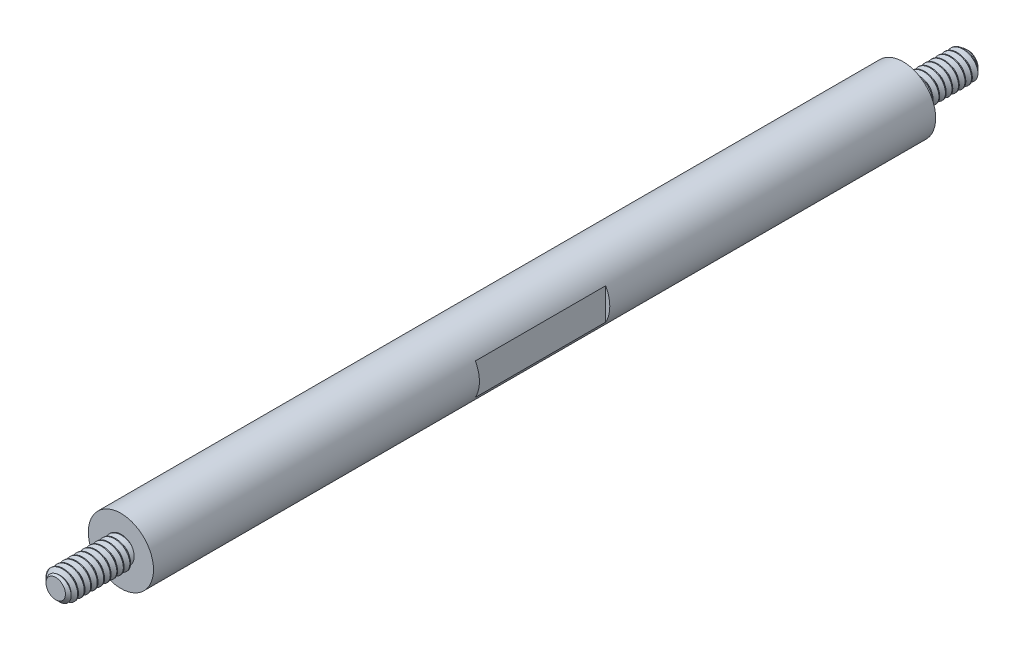
SolidWorks part; units mm, degrees
ref_plane "Front Plane" through (0, 0, 0) normal (0, 0, 1) x (1, 0, 0)
ref_plane "Top Plane" through (0, 0, 0) normal (0, 1, 0) x (1, 0, 0)
ref_plane "Right Plane" through (0, 0, 0) normal (1, 0, 0) x (0, 0, -1)
sketch "Sketch1" plane through (0, 0, 0) normal (0, 0, 1) x (1, 0, 0)
  line L1 (0, 3.6662) -> (-3.175, 1.8331) construction
  line L2 (-3.175, 1.8331) -> (-3.175, -1.8331) construction
  line L3 (-3.175, -1.8331) -> (0, -3.6662) construction
  line L4 (0, -3.6662) -> (3.175, -1.8331) construction
  line L5 (3.175, -1.8331) -> (3.175, 1.8331) construction
  line L6 (3.175, 1.8331) -> (0, 3.6662) construction
  circle A0 centre (0, 0) radius 3.175
  circle A1 centre (0, 0) radius 3.175 construction
  dimension "OD" = 6.35
extrude "Extrude1" add sketch "Sketch1" against normal blind 76.2
sketch "Sketch2" plane through (0, 0, 0) normal (0, 0, 1) x (1, 0, 0)
  circle A2 centre (0, 0) radius 1.4224
  dimension "D1" = 2.8448
extrude "Extrude2" add sketch "Sketch2" along normal blind 6.35 separate body
chamfer "Chamfer1" distance 0.4763 angle 45 1 edges at (1.4224, 0, 6.35)
sketch "Sketch3" plane through (0, 0, 0) normal (0, 0, -1) x (-1, 0, 0)
  circle A1 centre (0, 0) radius 1.4224
  circle A2 centre (0, 0) radius 1.4224
  point P0 (0, 1.4224)
  dimension "D1" = 0
curve "Helix/Spiral1" pitch 0.635 height 6.985 turns 11 parameters "Pitch"=0.635
sketch "Sketch4" plane through (0, 0, 0) normal (1, 0, 0) x (0, 0, -1)
  line L0 (-0.0397, 1.4911) -> (0.5953, 1.4911) construction
  line L1 (0.5953, 1.4911) -> (0.2778, 0.9412) construction
  line L2 (0.2778, 0.9412) -> (-0.0397, 1.4911) construction
  line L3 (0.2778, 1.4911) -> (0.2778, 1.4224) construction
  line L4 (0.2778, 1.01) -> (0.2778, 0.9412) construction
  line L5 (0, 1.4224) -> (0.5556, 1.4224) construction
  line L6 (-0.0198, 1.4568) -> (0.5755, 1.4568)
  line L7 (0.5755, 1.4568) -> (0.3175, 1.01)
  line L8 (0.3175, 1.01) -> (0.2381, 1.01)
  line L9 (0.2381, 1.01) -> (-0.0198, 1.4568)
  line L10 (-6.35, 1.4224) -> (-6.35, -1.4224) construction
  line L11 (-6.35, 0.9461) -> (-6.35, -0.9461) construction
  line L12 (0, 1.4224) -> (-5.8737, 1.4224) construction
  line L13 (-5.8737, -1.4224) -> (0, -1.4224) construction
  point P8 (0.2778, 1.4568)
  dimension "D1" = 0.635
  dimension "D2" = 0.0794
sweep "Cut-Sweep1" cut profiles "Sketch4" path "Helix/Spiral1" align with end faces yes
ref_plane "Plane1" through (0, 0, -38.1) normal (0, 0, 1) x (1, 0, 0)
ref_axis "Axis1" through (0, 3.4925, -38.1) along (0, -1, 0)
pattern_circular "CirPattern1" count 2 over 360 about axis through (0, 3.4925, -38.1) along (0, -1, 0) of bodies 108
combine bodies "Combine1" operation type add bodies to combine 111 102 108
sketch "Sketch5" plane through (0, 0, -38.1) normal (0, 0, 1) x (1, 0, 0)
  line L0 (-2.7781, 1.604) -> (-6.731, 1.604)
  line L1 (0, 3.2079) -> (-2.7781, 1.604) construction
  line L2 (-2.7781, 1.604) -> (-2.7781, -1.604)
  line L3 (-2.7781, -1.604) -> (0, -3.2079) construction
  line L4 (0, -3.2079) -> (2.7781, -1.604) construction
  line L5 (2.7781, -1.604) -> (2.7781, 1.604)
  line L6 (2.7781, 1.604) -> (0, 3.2079) construction
  line L7 (-6.731, 1.604) -> (-6.731, -1.604)
  line L10 (-6.731, -1.604) -> (-2.7781, -1.604)
  line L11 (0, 0) -> (-13.3063, 0) construction
  line L12 (2.7781, 1.604) -> (9.1789, 1.604)
  line L13 (9.1789, 1.604) -> (9.1789, -1.604)
  line L14 (9.1789, -1.604) -> (2.7781, -1.604)
  circle A0 centre (0, 0) radius 2.7781 construction
  dimension "D1" = 6.731
  dimension "Hexsize" = 5.5562
  dimension "D2" = 6.4008
extrude "Cut-Extrude1" cut sketch "Sketch5" against normal mid plane 12.7
equation "\"D3@Helix/Spiral1\" = \"Pitch@Helix/Spiral1\" +  \"Thread Length@Extrude2\""
equation "\"D1@Sketch4\" = \"Pitch@Helix/Spiral1\""
equation "\"D2@Sketch4\" = \"D1@Sketch4\" * 1 / 8"
equation "\"D1@Chamfer1\" = \"Pitch@Helix/Spiral1\"  * 6 / 8"
equation "\"D1@Sketch5\"=\"OD@sketch1\"+.015"
equation "\"D2@Sketch5\"=\"OD@sketch1\"+.002"
